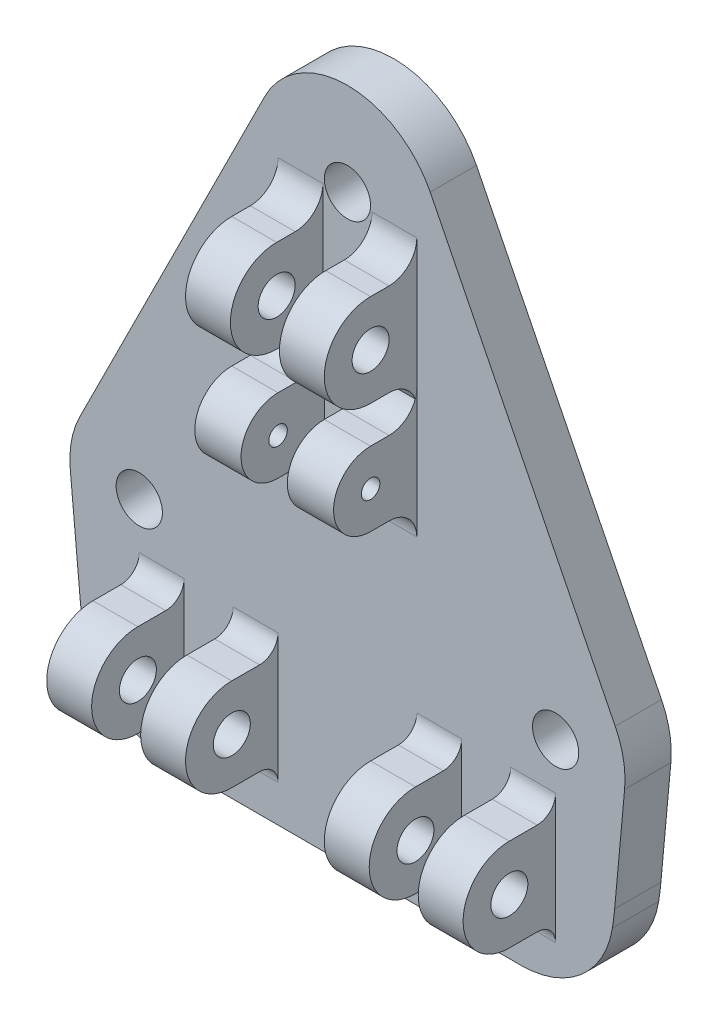
SolidWorks part; units mm, degrees
other "Markup1"
sketch "Sketch9" plane through (30, 50, 15) normal (0.9984, 0.0211, 0.0518) x (0.0521, -0.0136, -0.9985)
ref_plane "Front Plane" through (0, 0, 0) normal (0, 0, 1) x (1, 0, 0)
ref_plane "Top Plane" through (0, 0, 0) normal (0, 1, 0) x (1, 0, 0)
ref_plane "Right Plane" through (0, 0, 0) normal (1, 0, 0) x (0, 0, -1)
sketch "Sketch1" plane through (0, 0, 0) normal (0, 0, 1) x (1, 0, 0)
  line L0 (28.9443, 4.4721) -> (8.9443, 44.4721)
  line L1 (-8.9443, 44.4721) -> (-28.9443, 4.4721)
  line L2 (-29.958, -0.9159) -> (-28.8781, -12.6562)
  line L3 (28.8781, -12.6562) -> (29.958, -0.9159)
  arc A0 (8.9443, 44.4721) -> (-8.9443, 44.4721) centre (0, 40) ccw
  arc A1 (-28.8781, -12.6562) -> (28.8781, -12.6562) centre (0, -10) ccw
  arc A2 (28.9443, 4.4721) -> (29.958, -0.9159) centre (20, 0) cw
  arc A3 (-28.9443, 4.4721) -> (-29.958, -0.9159) centre (-20, 0) ccw
  dimension "D1" = 10
  dimension "D2" = 10
  dimension "D3" = 29
  dimension "D4" = 50
  dimension "D5" = 40
  dimension "D6" = 40
extrude "Boss-Extrude1" add sketch "Sketch1" along normal blind 5
sketch "Sketch2" plane through (0, 0, 5) normal (0, 0, 1) x (1, 0, 0)
  circle A0 centre (0, 40) radius 2.5
  circle A2 centre (22.5, 0) radius 2.5
  circle A3 centre (-22.5, 0) radius 2.5
  dimension "D1" = 5
  dimension "D2" = 45
  dimension "D3" = 22.5
  dimension "D5" = 40
extrude "Cut-Extrude1" cut sketch "Sketch2" against normal through all
sketch "Sketch3" plane through (0, 0, 0) normal (1, 0, 0) x (0, 0, -1)
  line L0 (-5, 22.4721) -> (-5, 14.4721)
  line L1 (-5, 4.4721) -> (-5, 44.4721) construction
  line L2 (-5, 14.4721) -> (-10, 14.4721)
  line L3 (-10, 22.4721) -> (-5, 22.4721)
  line L9 (-5, 44.4721) -> (0, 44.4721) construction
  arc A0 (-10, 14.4721) -> (-10, 22.4721) centre (-10, 18.4721) cw
  circle A3 centre (-10, 18.4721) radius 1
  dimension "D5" = 4
  dimension "D6" = 2
  dimension "D7" = 5
  dimension "D8" = 22
extrude "Boss-Extrude2" add sketch "Sketch3" along normal mid plane 15
sketch "Sketch5" plane through (0, 22.4721, 0) normal (0, 1, 0) x (1, 0, 0)
  line L0 (-7.5, -14) -> (7.5, -14) construction
  line L1 (-2.5, -23) -> (2.5, -23)
  line L2 (-2.5, -23) -> (-2.5, -5)
  line L3 (-2.5, -5) -> (2.5, -5)
  line L4 (2.5, -23) -> (2.5, -5)
  line L5 (-2.5, -23) -> (2.5, -5) construction
  line L6 (-2.5, -5) -> (2.5, -23) construction
  line L7 (-8.9443, -5) -> (8.9443, -5) construction
  point P0 (0, -14)
  dimension "D1" = 5
extrude "Cut-Extrude3" cut sketch "Sketch5" against normal up to surface (8 mm away) up to face at (0, 14.4721, 7.5)
fillet "Fillet1" radius 3 4 edges at (5, 14.4721, 5) (-5, 14.4721, 5) (5, 22.4721, 5) (-5, 22.4721, 5)
sketch "Sketch6" plane through (0, 0, 0) normal (1, 0, 0) x (0, 0, -1)
  line L0 (-5, 26.4721) -> (-5, 36.4721)
  line L1 (-5, 4.4721) -> (-5, 44.4721) construction
  line L2 (-5, 36.4721) -> (-10, 36.4721)
  line L3 (-10, 26.4721) -> (-5, 26.4721)
  line L4 (-5, 44.4721) -> (0, 44.4721) construction
  arc A0 (-10, 36.4721) -> (-10, 26.4721) centre (-10, 31.4721) ccw
  circle A1 centre (-10, 31.4721) radius 2
  point P8 (-10, 35.3227)
  dimension "D1" = 4
  dimension "D2" = 5
  dimension "D3" = 5
  dimension "D4" = 8
extrude "Boss-Extrude3" add sketch "Sketch6" along normal mid plane 15
sketch "Sketch7" plane through (0, 36.4721, 0) normal (0, 1, 0) x (1, 0, 0)
  line L0 (-7.5, -15) -> (7.5, -15) construction
  line L1 (-2.65, -25) -> (2.65, -25)
  line L2 (-2.65, -25) -> (-2.65, -5)
  line L3 (-2.65, -5) -> (2.65, -5)
  line L4 (2.65, -25) -> (2.65, -5)
  line L5 (-2.65, -25) -> (2.65, -5) construction
  line L6 (-2.65, -5) -> (2.65, -25) construction
  line L7 (7.5, -5) -> (-7.5, -5) construction
  point P0 (0, -15)
  dimension "D1" = 5.3
extrude "Cut-Extrude4" cut sketch "Sketch7" against normal up to surface (10 mm away) up to face at (0, 26.4721, 7.5)
fillet "Fillet2" radius 3 4 edges at (-5.075, 36.4721, 5) (5.075, 36.4721, 5) (-5.075, 26.4721, 5) (5.075, 26.4721, 5)
sketch "Sketch8" plane through (0, 0, 5) normal (0, 0, 1) x (1, 0, 0)
  line L0 (-25.923, -23) -> (25.923, -23)
  line L4 (28.8781, -12.6562) -> (29.958, -0.9159)
  line L5 (28.9443, 4.4721) -> (8.9443, 44.4721)
  line L6 (-8.9443, 44.4721) -> (-28.9443, 4.4721)
  line L7 (-29.958, -0.9159) -> (-28.8781, -12.6562)
  arc A4 (-28.8781, -12.6562) -> (28.8781, -12.6562) centre (0, -10) ccw
  arc A5 (29.958, -0.9159) -> (28.9443, 4.4721) centre (20, 0) ccw
  arc A6 (8.9443, 44.4721) -> (-8.9443, 44.4721) centre (0, 40) ccw
  arc A7 (-28.9443, 4.4721) -> (-29.958, -0.9159) centre (-20, 0) ccw
  arc A8 (-25.923, -23) -> (25.923, -23) centre (0, -10) ccw
  dimension "D2" = 16
  dimension "D1" = 0
extrude "Cut-Extrude5" cut sketch "Sketch8" against normal through all
fillet "Fillet4" radius 10 2 edges at (25.923, -23, 2.5) (-25.923, -23, 2.5)
sketch "Sketch10" plane through (0, 0, 0) normal (1, 0, 0) x (0, 0, -1)
  line L0 (-5, -17) -> (-10, -17)
  line L2 (-10, -7) -> (-5, -7)
  line L3 (-5, -12.6562) -> (-5, -0.9159) construction
  line L4 (-5, -7) -> (-5, -17)
  line L6 (0, -23) -> (-5, -23) construction
  arc A0 (-10, -17) -> (-10, -7) centre (-10, -12) cw
  circle A1 centre (-10, -12) radius 2
  point P12 (0, 0)
  dimension "D1" = 4
  dimension "D2" = 5
  dimension "D3" = 5
  dimension "D4" = 6
extrude "Boss-Extrude4" add sketch "Sketch10" along normal mid plane 45
sketch "Sketch11" plane through (0, -17, 0) normal (0, -1, 0) x (1, 0, 0)
  line L0 (22.5, 15) -> (-22.5, 15) construction
  line L1 (-7.5, 25) -> (7.5, 25)
  line L2 (-7.5, 25) -> (-7.5, 5)
  line L3 (-7.5, 5) -> (7.5, 5)
  line L4 (7.5, 25) -> (7.5, 5)
  line L5 (-7.5, 25) -> (7.5, 5) construction
  line L6 (-7.5, 5) -> (7.5, 25) construction
  line L7 (18.7617, 5) -> (-18.7617, 5) construction
  line L9 (-17.65, 25) -> (-12.35, 25)
  line L10 (-17.65, 25) -> (-17.65, 5)
  line L11 (-17.65, 5) -> (-12.35, 5)
  line L12 (-12.35, 25) -> (-12.35, 5)
  line L13 (-17.65, 25) -> (-12.35, 5) construction
  line L14 (-17.65, 5) -> (-12.35, 25) construction
  point P0 (0, 15)
  point P9 (-15, 15)
  point P14 (10.6957, 15)
  dimension "D1" = 15
  dimension "D2" = 5.3
  dimension "D3" = 15
extrude "Cut-Extrude6" cut sketch "Sketch11" against normal up to surface (10 mm away) up to face at (0, -7, 7.5)
mirror "Mirror1" about plane through (0, 0, 0) normal (1, 0, 0) of "Cut-Extrude6"
fillet "Fillet5" radius 2 8 edges at (20.075, -17, 5) (-20.075, -17, 5) (-20.075, -7, 5) (-9.925, -7, 5) (9.925, -7, 5) (20.075, -7, 5) (9.925, -17, 5) (-9.925, -17, 5)
